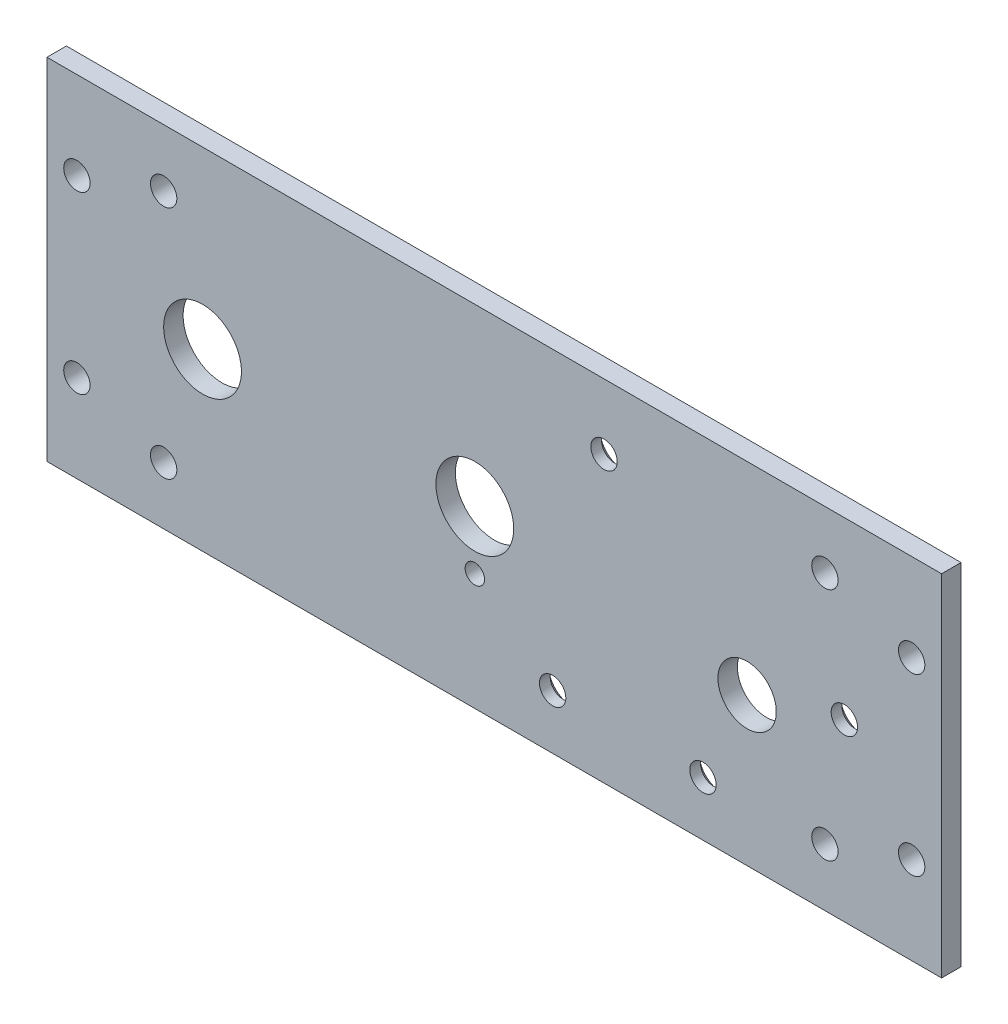
SolidWorks part; units mm, degrees
ref_plane "Front Plane" through (0, 0, 0) normal (0, 0, 1) x (1, 0, 0)
ref_plane "Top Plane" through (0, 0, 0) normal (0, 1, 0) x (1, 0, 0)
ref_plane "Right Plane" through (0, 0, 0) normal (1, 0, 0) x (0, 0, -1)
sketch "Sketch1" plane through (0, 0, 0) normal (0, 0, 1) x (1, 0, 0)
  line L4 (0, 57.15) -> (-146.05, 57.15)
  line L5 (-146.05, 57.15) -> (-146.05, 0)
  line L6 (-146.05, 0) -> (0, 0)
  line L7 (0, 0) -> (0, 57.15)
  line L8 (0, 57.15) -> (-146.05, 57.15)
  line L9 (-146.05, 57.15) -> (-146.05, 0)
  line L10 (-146.05, 0) -> (0, 0)
  line L11 (0, 0) -> (0, 57.15)
  dimension "D1" = 0
extrude "Boss-Extrude1" add sketch "Sketch1" against normal blind 3.175
hole_wizard "#6 Clearance Hole1" positions "Sketch3" profile "Sketch2" hole size "#6" standard "ANSI Inch" end condition through all
sketch "Sketch3" plane through (0, 0, -3.175) normal (0, 0, -1) x (-1, 0, 0)
  point P0 (4.8895, 42.8625)
  point P3 (141.1605, 42.8625)
  point P6 (141.1605, 14.2875)
  point P9 (4.8895, 14.2875)
  point P12 (19.05, 47.752)
  point P15 (19.05, 9.398)
  point P18 (127, 9.398)
  point P21 (127, 47.752)
sketch "Sketch2" plane through (-4.8895, 42.8625, -3.175) normal (1, 0, 0) x (0, 1, 0)
  line L0 (0, 0) -> (0, 3.175)
  line L1 (0, 3.175) -> (2.1526, 3.175)
  line L2 (2.1526, 3.175) -> (2.1526, 0)
  line L5 (2.1526, 0) -> (0, 0)
  line L11 (0, -6.35) -> (0, 107.95) construction
  dimension "Thru Hole Dia." = 4.3053
  dimension "Thru Hole Depth" = 3.175
hole_wizard "1/2 (0.5) Diameter Hole1" positions "Sketch5" profile "Sketch4" hole size "1/2" standard "ANSI Inch" end condition through all
sketch "Sketch5" plane through (0, 0, -3.175) normal (0, 0, -1) x (-1, 0, 0)
  point P0 (76.2, 28.575)
  point P3 (120.65, 28.575)
sketch "Sketch4" plane through (-76.2, 28.575, -3.175) normal (1, 0, 0) x (0, 1, 0)
  line L0 (0, 0) -> (0, 3.175)
  line L1 (0, 3.175) -> (6.35, 3.175)
  line L2 (6.35, 3.175) -> (6.35, 0)
  line L5 (6.35, 0) -> (0, 0)
  line L11 (0, -6.35) -> (0, 107.95) construction
  dimension "Thru Hole Dia." = 12.7
  dimension "Thru Hole Depth" = 3.175
hole_wizard "3/8 (0.375) Diameter Hole1" positions "Sketch7" profile "Sketch6" hole size "3/8" standard "ANSI Inch" end condition through all
sketch "Sketch7" plane through (0, 0, -3.175) normal (0, 0, -1) x (-1, 0, 0)
  point P0 (31.75, 24.13)
sketch "Sketch6" plane through (-31.75, 24.13, -3.175) normal (1, 0, 0) x (0, 1, 0)
  line L0 (0, 0) -> (0, 3.175)
  line L1 (0, 3.175) -> (4.7625, 3.175)
  line L2 (4.7625, 3.175) -> (4.7625, 0)
  line L5 (4.7625, 0) -> (0, 0)
  line L11 (0, -6.35) -> (0, 107.95) construction
  dimension "Thru Hole Dia." = 9.525
  dimension "Thru Hole Depth" = 3.175
hole_wizard "1/8 (0.125) Diameter Hole1" positions "Sketch9" profile "Sketch8" hole size "1/8" standard "ANSI Inch" end condition through all
sketch "Sketch9" plane through (0, 0, -3.175) normal (0, 0, -1) x (-1, 0, 0)
  point P0 (76.2, 19.05)
sketch "Sketch8" plane through (-76.2, 19.05, -3.175) normal (1, 0, 0) x (0, 1, 0)
  line L0 (0, 0) -> (0, 3.175)
  line L1 (0, 3.175) -> (1.5875, 3.175)
  line L2 (1.5875, 3.175) -> (1.5875, 0)
  line L5 (1.5875, 0) -> (0, 0)
  line L11 (0, -6.35) -> (0, 107.95) construction
  dimension "Thru Hole Dia." = 3.175
  dimension "Thru Hole Depth" = 3.175
hole_wizard "CSK for #6 Flat Head Machine Screw (100)2" positions "Sketch13" profile "Sketch14" countersink size "#6" standard "ANSI Inch" end condition through all
sketch "Sketch13" plane through (0, 0, -3.175) normal (0, 0, -1) x (-1, 0, 0)
  point P0 (63.5, 8.89)
  point P2 (55.108, 46.4933)
  point P4 (15.875, 28.58)
  point P6 (38.95, 8.89)
sketch "Sketch14" plane through (-63.5, 8.89, -3.175) normal (1, 0, 0) x (0, 1, 0)
  line L0 (0, 0) -> (0, 3.175)
  line L1 (0, 3.175) -> (2.1526, 3.175)
  line L2 (2.1526, 3.175) -> (2.1526, 1.4209)
  line L3 (2.1526, 1.4209) -> (3.846, 0)
  line L5 (3.846, 0) -> (0, 0)
  line L6 (-2.1526, 1.4209) -> (-3.846, 0) construction
  line L11 (0, -6.35) -> (0, 107.95) construction
  dimension "Thru Hole Dia." = 4.3053
  dimension "Thru Hole Depth" = 3.175
  dimension "Near C'Sink Dia." = 7.692
  dimension "Near C'Sink Angle" = 100
